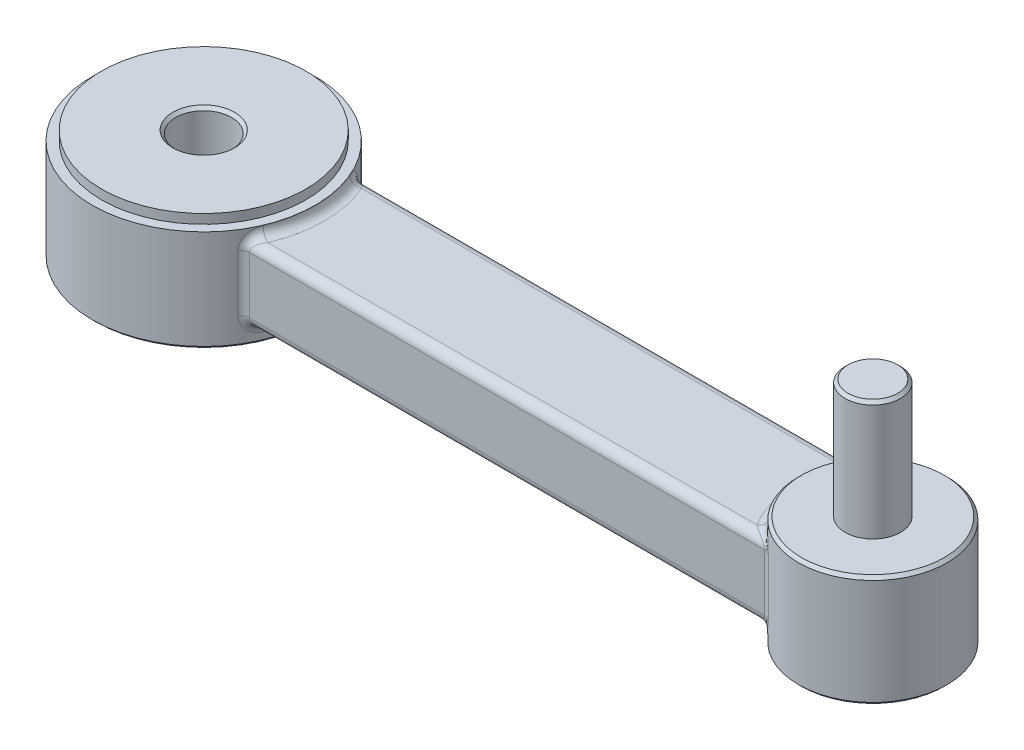
SolidWorks part; units mm, degrees
ref_plane "Front Plane" through (0, 0, 0) normal (0, 0, 1) x (1, 0, 0)
ref_plane "Top Plane" through (0, 0, 0) normal (0, 1, 0) x (1, 0, 0)
ref_plane "Right Plane" through (0, 0, 0) normal (1, 0, 0) x (0, 0, -1)
sketch "Sketch2" plane through (0, 0, 0) normal (0, 1, 0) x (1, 0, 0)
  circle A0 centre (0, 0) radius 19.05
  dimension "D1" = 38.1
sketch "Sketch4" plane through (0, 0, 0) normal (0, 1, 0) x (1, 0, 0)
  line L0 (0, 0) -> (114.3, 0) construction
  circle A0 centre (114.3, 0) radius 12.7
  dimension "D2" = 25.4
  dimension "D1" = 114.3
extrude "Boss-Extrude1" add sketch "Sketch2" along normal mid plane 19.05
sketch "Sketch6" plane through (0, 9.525, 0) normal (0, 1, 0) x (1, 0, 0)
  circle A0 centre (0, 0) radius 17.4625
  circle A1 centre (0, 0) radius 19.05
  dimension "D1" = 34.925
extrude "Cut-Extrude1" cut sketch "Sketch6" against normal blind 1.6002
extrude "Boss-Extrude2" add sketch "Sketch4" along normal mid plane 19.05
sketch "Sketch9" plane through (0, 0, 0) normal (0, 1, 0) x (1, 0, 0)
  line L0 (19.05, 0) -> (101.6, 0) construction
  line L1 (16.4978, 9.525) -> (105.8997, 9.525)
  line L2 (16.4978, -9.525) -> (105.8997, -9.525)
  circle A0 centre (0, 0) radius 19.05 construction
  circle A1 centre (114.3, 0) radius 12.7 construction
  arc A2 (16.4978, 9.525) -> (16.4978, -9.525) centre (0, 0) cw
  arc A3 (105.8997, -9.525) -> (105.8997, 9.525) centre (114.3, 0) cw
  dimension "D1" = 9.525
extrude "Boss-Extrude4" add sketch "Sketch9" along normal mid plane 12.7
sketch "Sketch10" plane through (0, 9.525, 0) normal (0, 1, 0) x (1, 0, 0)
  circle A0 centre (114.3, 0) radius 4.7371
  dimension "D1" = 9.4742
extrude "Boss-Extrude5" add sketch "Sketch10" along normal blind 20.32
sketch "Sketch11" plane through (0, 9.525, 0) normal (0, 1, 0) x (1, 0, 0)
  circle A0 centre (0, 0) radius 4.7625
  dimension "D1" = 9.525
extrude "Cut-Extrude2" cut sketch "Sketch11" against normal through all
fillet "Fillet1" radius 1.524 12 edges at (105.8997, 0, -9.525) (16.4978, 0, -9.525) (101.6, -6.35, 0) (61.1988, -6.35, -9.525) (19.05, -6.35, 0) (16.4978, 0, 9.525) (105.8997, 0, 9.525) (61.1988, -6.35, 9.525) (61.1988, 6.35, -9.525) (101.6, 6.35, 0) (61.1988, 6.35, 9.525) (19.05, 6.35, 0)
chamfer "Chamfer1" distance 0.508 angle 45 5 edges at (0, -9.525, 19.05) (0, 9.525, 4.7625) (114.3, -9.525, 12.7) (114.3, 9.525, 12.7) (114.3, 29.845, 4.7371)
